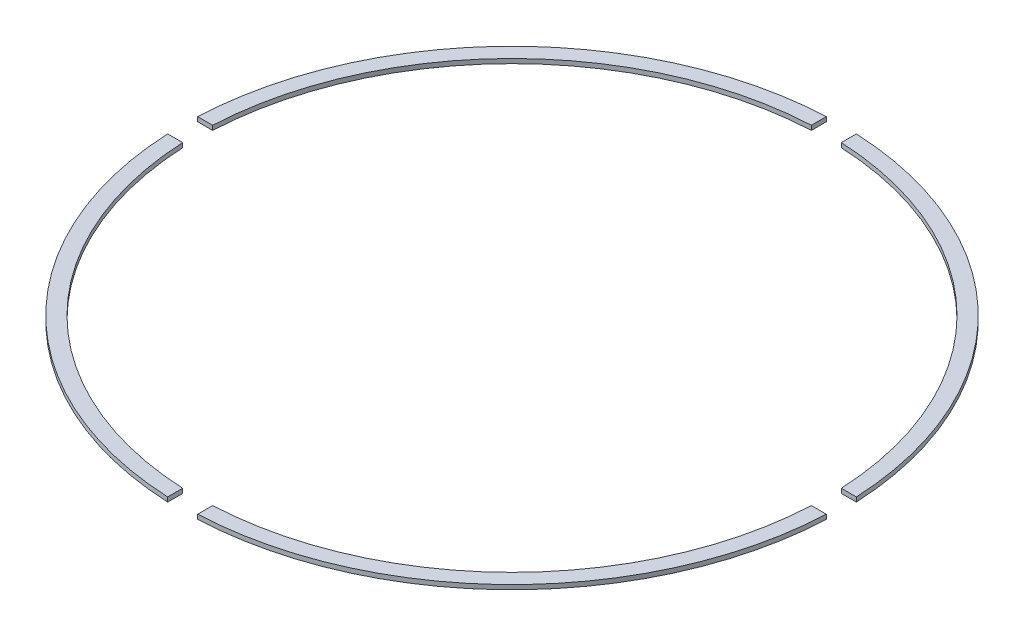
SolidWorks part; units mm, degrees
ref_plane "Front Plane" through (0, 0, 0) normal (0, 0, 1) x (1, 0, 0)
ref_plane "Top Plane" through (0, 0, 0) normal (0, 1, 0) x (1, 0, 0)
ref_plane "Right Plane" through (0, 0, 0) normal (1, 0, 0) x (0, 0, -1)
sketch "Sketch1" plane through (0, 0, 0) normal (0, 1, 0) x (1, 0, 0)
  circle A0 centre (0, 0) radius 210
  circle A1 centre (0, 0) radius 220
  dimension "D1" = 420
  dimension "D2" = 440
extrude "Boss-Extrude1" add sketch "Sketch1" along normal mid plane 3
sketch "pitch" plane through (0, 0, 0) normal (0, 1, 0) x (1, 0, 0)
  line L0 (-215, 0) -> (215, 0) construction
  dimension "D1" = 430
sketch "circle" plane through (0, 0, 0) normal (0, 1, 0) x (1, 0, 0)
  circle A0 centre (0, 0) radius 215 construction
sketch "Sketch2" plane through (0, 0, 0) normal (0, 1, 0) x (1, 0, 0)
  line L0 (-215, 0) -> (215, 0) construction
  line L1 (10, 220) -> (-10, 220)
  line L2 (10, 220) -> (10, -220)
  line L3 (10, -220) -> (-10, -220)
  line L4 (-10, 220) -> (-10, -220)
  line L5 (10, 220) -> (-10, -220) construction
  line L6 (10, -220) -> (-10, 220) construction
  line L8 (220, 10) -> (-220, 10)
  line L9 (220, 10) -> (220, -10)
  line L10 (220, -10) -> (-220, -10)
  line L11 (-220, 10) -> (-220, -10)
  line L12 (220, 10) -> (-220, -10) construction
  line L13 (220, -10) -> (-220, 10) construction
  circle A0 centre (0, 0) radius 220 construction
  point P0 (0, 0)
  point P10 (0, 0)
  dimension "D1" = 20
  dimension "D2" = 20
extrude "quadruple" cut sketch "Sketch2" against normal through all both and the other way through all contours L8 L11 L10 L9 | L4 L3 L2 L1
sketch "Sketch3" plane through (0, 0, 0) normal (0, 1, 0) x (1, 0, 0)
  line L0 (0, 220) -> (0, -220) construction
  circle A0 centre (0, 0) radius 220 construction
  circle A1 centre (0, 0) radius 220
